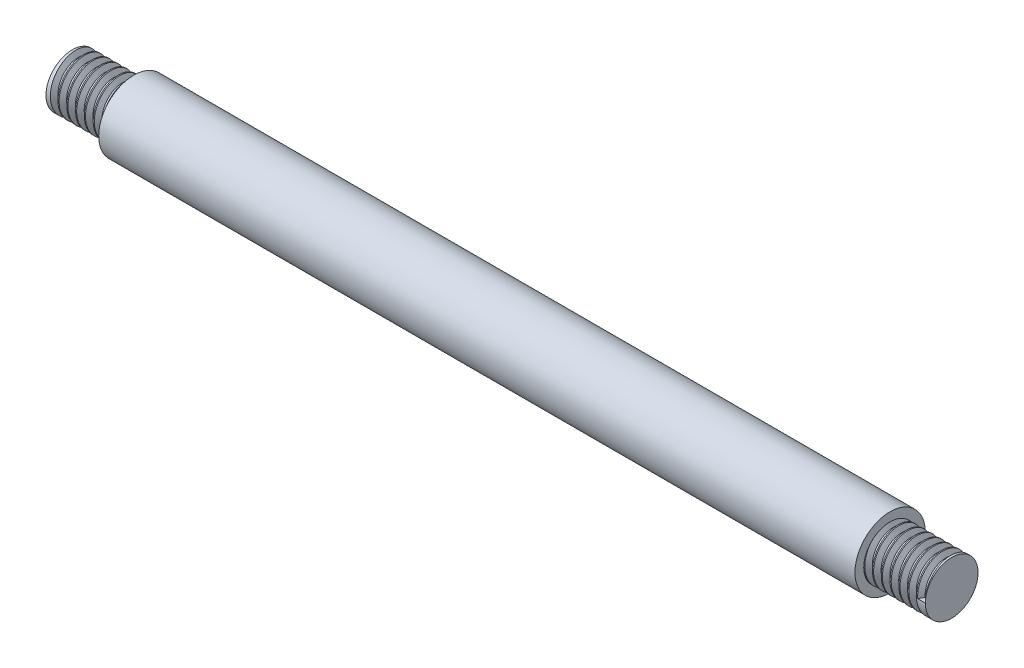
SolidWorks part; units mm, degrees
ref_plane "Front Plane" through (0, 0, 0) normal (0, 0, 1) x (1, 0, 0)
ref_plane "Top Plane" through (0, 0, 0) normal (0, 1, 0) x (1, 0, 0)
ref_plane "Right Plane" through (0, 0, 0) normal (1, 0, 0) x (0, 0, -1)
sketch "Sketch1" plane through (0, 0, 0) normal (0, 1, 0) x (1, 0, 0)
  line L0 (0, 2) -> (0, 0) construction
  line L1 (-50, 1.5) -> (50, 1.5)
  line L2 (-50, 1.5) -> (-50, -1.5)
  line L3 (-50, -1.5) -> (50, -1.5)
  line L4 (50, 1.5) -> (50, -1.5)
  line L5 (-50, 1.5) -> (50, -1.5) construction
  line L6 (-50, -1.5) -> (50, 1.5) construction
  line L12 (-43, 2.5) -> (43, 2.5)
  line L13 (-43, 2.5) -> (-43, 1.5)
  line L14 (-43, 1.5) -> (43, 1.5)
  line L15 (43, 2.5) -> (43, 1.5)
  line L16 (-43, 2.5) -> (43, 1.5) construction
  line L17 (-43, 1.5) -> (43, 2.5) construction
  point P0 (0, 0)
  dimension "D1" = 100
  dimension "D2" = 3
  dimension "D3" = 1
  dimension "D4" = 86
revolve "Revolve2" add sketch "Sketch1" angle 360 about L3 region at (0, 0, 0) region at (0, 0, -2)
thread "Thread2" pitch 1 method cut profile "Thread Profile2" start angle 0, offset 0, length 7, pitch 1, diameter 6
ref_plane "Plane2" through (-50, 0, -1.5) normal (0, -1, 0) x (0, 0, -1)
sketch "Thread Profile2" plane through (-50, 0, -1.5) normal (0, -1, 0) x (0, 0, -1)
  line L0 (0, 0) -> (0, 1) construction
  line L11 (0, 0) -> (0, 0.875)
  line L12 (0, 0.875) -> (-0.5413, 0.5625)
  line L13 (-0.5413, 0.5625) -> (-0.5413, 0.3125)
  line L15 (-0.5413, 0.3125) -> (0, 0)
  line L17 (-0.5413, 0.4375) -> (0, 0.4375) construction
  point P2 (0, 0)
  dimension "Pitch" = 1
  dimension "Profile_Angle" = 60
  dimension "Profile_Land" = 0.25
  dimension "Profile_Height" = 0.5413
thread "Thread3" pitch 1 method cut profile "Thread Profile3" start angle 0, offset 0, length 7, pitch 1, diameter 6
ref_plane "Plane3" through (50, 0, 4.5) normal (0, -1, 0) x (0, 0, 1)
sketch "Thread Profile3" plane through (50, 0, 4.5) normal (0, -1, 0) x (0, 0, 1)
  line L0 (0, 0) -> (0, 1) construction
  line L11 (0, 0) -> (0, 0.875)
  line L12 (0, 0.875) -> (-0.5413, 0.5625)
  line L13 (-0.5413, 0.5625) -> (-0.5413, 0.3125)
  line L15 (-0.5413, 0.3125) -> (0, 0)
  line L17 (-0.5413, 0.4375) -> (0, 0.4375) construction
  point P2 (0, 0)
  dimension "Pitch" = 1
  dimension "Profile_Angle" = 60
  dimension "Profile_Land" = 0.25
  dimension "Profile_Height" = 0.5413
